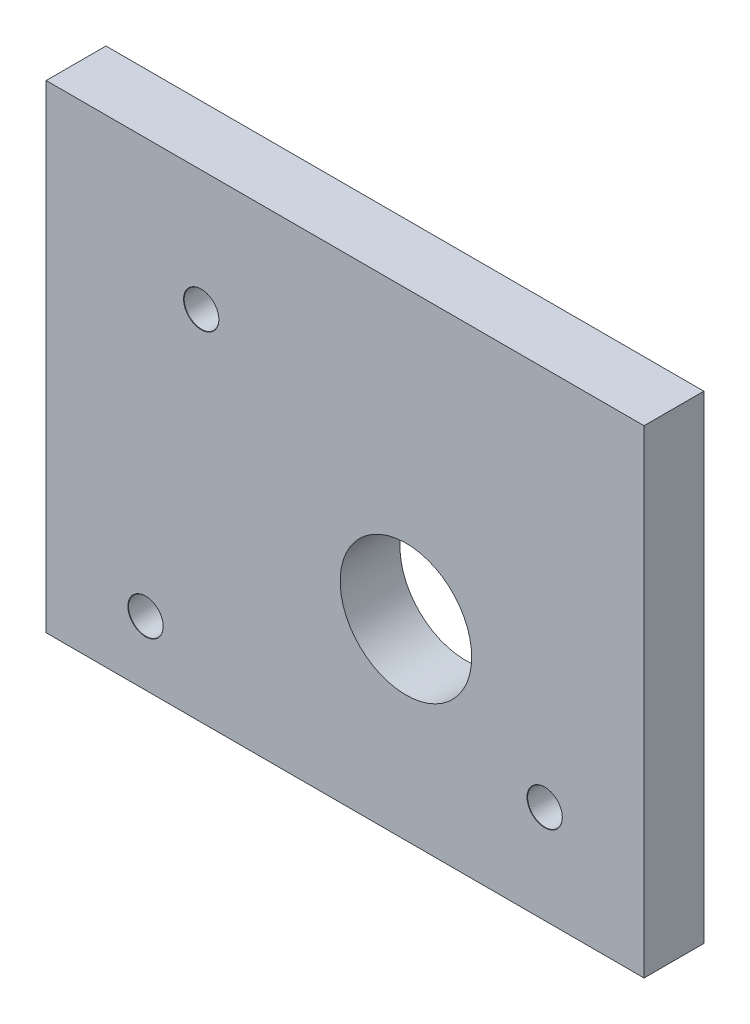
SolidWorks part; units mm, degrees
ref_plane "Front Plane" through (0, 0, 0) normal (0, 0, 1) x (1, 0, 0)
ref_plane "Top Plane" through (0, 0, 0) normal (0, 1, 0) x (1, 0, 0)
ref_plane "Right Plane" through (0, 0, 0) normal (1, 0, 0) x (0, 0, -1)
sketch "hole_reference" plane through (0, 0, 0) normal (0, 0, 1) x (1, 0, 0)
  line L0 (0, 0) -> (33.3777, 0) construction
  line L1 (33.3777, 0) -> (33.3777, 2.86) construction
  point P0 (0, 0)
  point P1 (33.3777, 2.86)
  point P3 (4.6551, 24.5628)
  point P4 (21.7754, 10.6949)
  dimension "D1" = 33.5
  dimension "D2" = 25
  dimension "D3" = 36
  dimension "D4" = 2.86
  dimension "D5" = 14
  dimension "D6" = 24.26
sketch "Sketch1" plane through (0, 0, 0) normal (0, 0, 1) x (1, 0, 0)
  line L0 (4.6551, 24.5628) -> (4.6551, 0) construction
  line L1 (-8.3112, 34.6544) -> (41.6888, 34.6544)
  line L2 (-8.3112, 34.6544) -> (-8.3112, -5.3456)
  line L3 (-8.3112, -5.3456) -> (41.6888, -5.3456)
  line L4 (41.6888, 34.6544) -> (41.6888, -5.3456)
  line L5 (0, 0) -> (33.3777, 0) construction
  line L8 (16.6888, 0) -> (16.6888, -5.3456) construction
  point P7 (16.6888, 0)
  dimension "D1" = 40
  dimension "D2" = 50
  dimension "D3" = 10.0916
extrude "Boss-Extrude1" add sketch "Sketch1" along normal mid plane 5 contours L1 L4 L3 L2
hole_wizard "M2.5 Clearance Hole2" positions "Sketch2" profile "Sketch3" hole size "M2.5" standard "ANSI Metric" end condition through all
sketch "Sketch2" plane through (0, 0, 2.5) normal (0, 0, 1) x (1, 0, 0)
  point P0 (4.6551, 24.5628)
  point P6 (33.3777, 2.86)
  point P19 (0, 0)
sketch "Sketch3" plane through (4.6551, 24.5628, 2.5) normal (1, 0, 0) x (0, -1, 0)
  line L0 (0, 0) -> (0, 5)
  line L1 (0, 5) -> (1.45, 5)
  line L2 (1.45, 5) -> (1.45, 0.025)
  line L3 (1.45, 0.025) -> (1.475, 0)
  line L5 (1.475, 0) -> (0, 0)
  line L6 (-1.45, 0.025) -> (-1.475, 0) construction
  line L11 (0, -6.35) -> (0, 107.95) construction
  dimension "Thru Hole Dia." = 2.9
  dimension "Thru Hole Depth" = 5
  dimension "Near C'Sink Dia." = 2.95
  dimension "Near C'Sink Angle" = 90
sketch "Sketch4" plane through (0, 0, 2.5) normal (0, 0, 1) x (1, 0, 0)
  circle A0 centre (21.7754, 10.6949) radius 5.5
  dimension "D1" = 11
extrude "Cut-Extrude1" cut sketch "Sketch4" against normal through all
